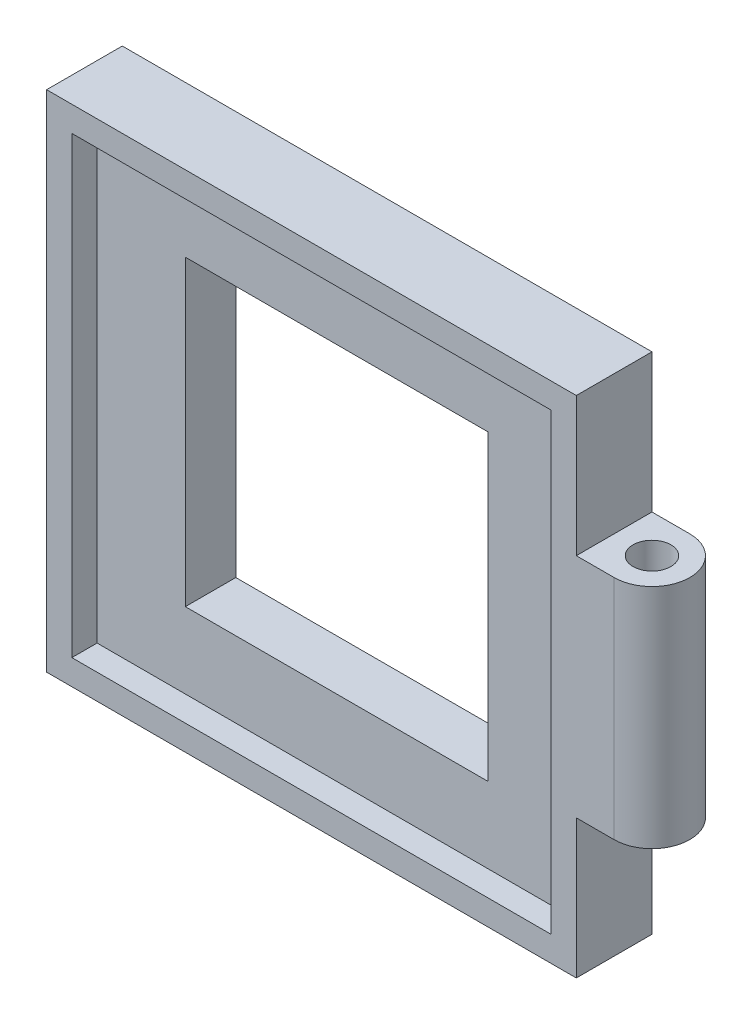
SolidWorks part; units mm, degrees
ref_plane "Alzado" through (0, 0, 0) normal (0, 0, 1) x (1, 0, 0)
ref_plane "Planta" through (0, 0, 0) normal (0, 1, 0) x (1, 0, 0)
ref_plane "Vista lateral" through (0, 0, 0) normal (1, 0, 0) x (0, 0, -1)
sketch "Croquis1" plane through (0, 0, 0) normal (0, 1, 0) x (1, 0, 0)
  line L1 (-10.5, -1.5) -> (10.5, -1.5)
  line L2 (-10.5, -1.5) -> (-10.5, 1.5)
  line L3 (-10.5, 1.5) -> (10.5, 1.5)
  line L4 (10.5, -1.5) -> (10.5, 1.5)
  line L5 (-10.5, -1.5) -> (10.5, 1.5) construction
  line L6 (-10.5, 1.5) -> (10.5, -1.5) construction
  point P0 (0, 0)
  dimension "D1" = 3
  dimension "D2" = 21
extrude "Saliente-Extruir1" add sketch "Croquis1" along normal blind 20
ref_plane "Plano1" through (0, 10, 0) normal (0, 1, 0) x (1, 0, 0)
sketch "Croquis3" plane through (0, 10, 0) normal (0, 1, 0) x (1, 0, 0)
  line L0 (10.5, 1.5) -> (13.5, -1.5) construction
  line L1 (10.5, 1.5) -> (13.5, 1.5) construction
  line L2 (10.5, 1.5) -> (10.5, -1.5)
  line L3 (10.5, -1.5) -> (13.5, -1.5) construction
  line L4 (13.5, 1.5) -> (13.5, -1.5) construction
  line L5 (10.5, 1.5) -> (12, 1.5)
  line L6 (10.5, -1.5) -> (12, -1.5)
  arc A0 (12, -1.5) -> (12, 1.5) centre (12, 0) ccw
  circle A1 centre (12, 0) radius 0.75
  dimension "D2" = 1.5
  dimension "D1" = 3
extrude "Saliente-Extruir2" add sketch "Croquis3" along normal blind 4.5 and the other way blind 4.5
sketch "Croquis5" plane through (0, 0, 1.5) normal (0, 0, 1) x (1, 0, 0)
  line L0 (2.2, 10) -> (-2.2, 10) construction
  line L1 (-9.5, 1) -> (9.5, 1)
  line L2 (-9.5, 1) -> (-9.5, 19)
  line L3 (-9.5, 19) -> (9.5, 19)
  line L4 (9.5, 1) -> (9.5, 19)
  line L5 (-9.5, 1) -> (9.5, 19) construction
  line L6 (-9.5, 19) -> (9.5, 1) construction
  point P0 (0, 10)
  dimension "D1" = 19
  dimension "D2" = 18
extrude "Cortar-Extruir2" cut sketch "Croquis5" against normal up to next
sketch "Croquis6" plane through (0, 0, -1.5) normal (0, 0, -1) x (-1, 0, 0)
  line L0 (9.5, 19) -> (-9.5, 1) construction
  line L1 (-9.5, 19) -> (9.5, 19)
  line L2 (-9.5, 19) -> (-9.5, 1)
  line L3 (-9.5, 1) -> (9.5, 1)
  line L4 (9.5, 19) -> (9.5, 1)
  line L5 (-6, 4) -> (6, 4)
  line L6 (-6, 4) -> (-6, 16)
  line L7 (-6, 16) -> (6, 16)
  line L8 (6, 4) -> (6, 16)
  line L9 (-6, 4) -> (6, 16) construction
  line L10 (-6, 16) -> (6, 4) construction
  point P6 (0, 10)
  point P11 (-4.4402, 14.1873)
  point P12 (0, 10)
  dimension "D1" = 3
extrude "Saliente-Extruir3" add sketch "Croquis6" against normal blind 2
